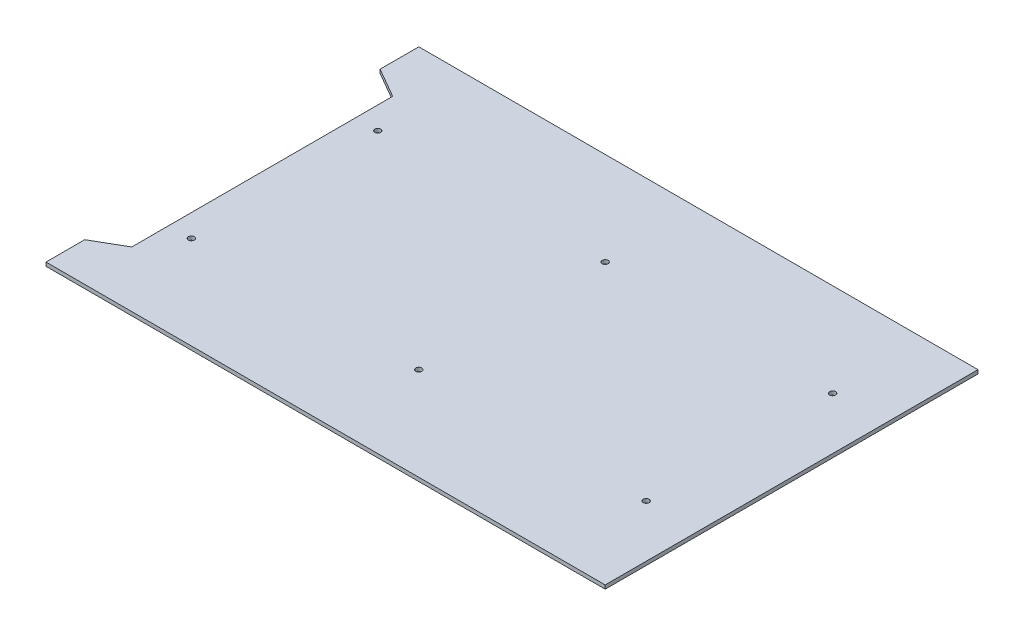
SolidWorks part; units mm, degrees
material "Stainless Steel (ferritic)"
ref_plane "Front Plane" through (0, 0, 0) normal (0, 0, 1) x (1, 0, 0)
ref_plane "Top Plane" through (0, 0, 0) normal (0, 1, 0) x (1, 0, 0)
ref_plane "Right Plane" through (0, 0, 0) normal (1, 0, 0) x (0, 0, -1)
sketch "Sketch1" plane through (0, 0, 0) normal (0, 1, 0) x (1, 0, 0)
  line L1 (-375, 250) -> (375, 250)
  line L2 (-375, 250) -> (-375, -250)
  line L3 (-375, -250) -> (375, -250)
  line L4 (375, 250) -> (375, -250)
  line L5 (-375, 250) -> (375, -250) construction
  line L6 (-375, -250) -> (375, 250) construction
  point P0 (0, 0)
extrude "Boss-Extrude1" add sketch "Sketch1" along normal blind 5
sketch "Sketch2" plane through (0, 5, 0) normal (0, 1, 0) x (1, 0, 0)
  line L0 (375, 250) -> (-375, 250) construction
  line L1 (375, -250) -> (375, 250) construction
  circle A0 centre (305, 125) radius 4
  dimension "D1" = 125
  dimension "D2" = 70
  dimension "D3" = 8
extrude "Cut-Extrude1" cut sketch "Sketch2" against normal blind 10
sketch "Sketch3" plane through (0, 5, 0) normal (0, 1, 0) x (1, 0, 0)
  line L0 (-375, -250) -> (375, -250) construction
  line L1 (375, -250) -> (375, 250) construction
  circle A0 centre (305, -125) radius 4
  dimension "D1" = 125
  dimension "D2" = 70
  dimension "D3" = 8
extrude "Cut-Extrude2" cut sketch "Sketch3" against normal blind 10
sketch "Sketch4" plane through (0, 5, 0) normal (0, 1, 0) x (1, 0, 0)
  line L0 (375, -250) -> (375, 250) construction
  line L1 (375, 250) -> (-375, 250) construction
  circle A0 centre (0, 125) radius 4
  dimension "D1" = 8
  dimension "D2" = 375
  dimension "D3" = 125
extrude "Cut-Extrude3" cut sketch "Sketch4" against normal blind 10
sketch "Sketch5" plane through (0, 5, 0) normal (0, 1, 0) x (1, 0, 0)
  circle A0 centre (0, -125) radius 4
extrude "Cut-Extrude4" cut sketch "Sketch5" against normal blind 10
sketch "Sketch6" plane through (0, 5, 0) normal (0, 1, 0) x (1, 0, 0)
  line L0 (-375, 250) -> (-375, -250) construction
  line L1 (375, 250) -> (-375, 250) construction
  circle A0 centre (-305, 125) radius 4
  dimension "D1" = 70
  dimension "D2" = 125
  dimension "D3" = 8
extrude "Cut-Extrude5" cut sketch "Sketch6" against normal blind 10
sketch "Sketch7" plane through (0, 5, 0) normal (0, 1, 0) x (1, 0, 0)
  line L0 (-375, 250) -> (-375, -250) construction
  line L1 (-375, -250) -> (375, -250) construction
  circle A0 centre (-305, -125) radius 4
  dimension "D1" = 8
  dimension "D2" = 70
  dimension "D3" = 125
extrude "Cut-Extrude6" cut sketch "Sketch7" against normal blind 10 contours A0
sketch "Sketch9" plane through (0, 5, 0) normal (0, 1, 0) x (1, 0, 0)
  line L0 (-375, 250) -> (0, 250) construction
  line L1 (375, 250) -> (-375, 250) construction
  line L2 (-187.5, 250) -> (-187.5, -250) construction
  line L3 (-375, -250) -> (375, -250) construction
sketch "Sketch10" plane through (0, 5, 0) normal (0, 1, 0) x (1, 0, 0)
  line L0 (-375, 0) -> (-322.1323, 0) construction
  line L1 (-375, 250) -> (-375, -250) construction
  line L2 (-335, 175) -> (-335, -175)
  line L3 (-335, 175) -> (-375, 198.094)
  line L4 (-335, -175) -> (-375, -198.094)
  line L5 (-375, 198.094) -> (-375, -198.094)
  point P10 (-335, 0)
  dimension "D1" = 175
  dimension "D2" = 40
  dimension "D3" = 120
extrude "Cut-Extrude7" cut sketch "Sketch10" against normal up to next
